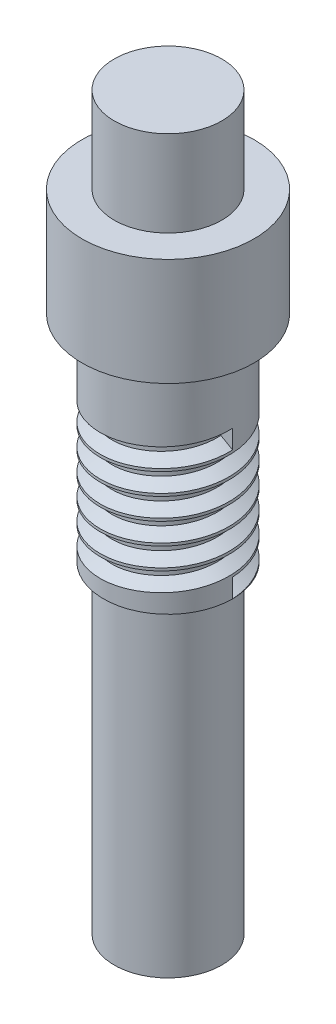
SolidWorks part; units mm, degrees
material "Plain Carbon Steel"
ref_plane "Front Plane" through (0, 0, 0) normal (0, 0, 1) x (1, 0, 0)
ref_plane "Top Plane" through (0, 0, 0) normal (0, 1, 0) x (1, 0, 0)
ref_plane "Right Plane" through (0, 0, 0) normal (1, 0, 0) x (0, 0, -1)
sketch "Sketch1" plane through (0, 0, 0) normal (0, 1, 0) x (1, 0, 0)
  circle A0 centre (0, 0) radius 4
  dimension "D1" = 8
extrude "Boss-Extrude1" add sketch "Sketch1" along normal blind 30
sketch "Sketch8" plane through (0, 0, 0) normal (0, -1, 0) x (1, 0, 0)
  circle A0 centre (0, 0) radius 3
  circle A1 centre (0, 0) radius 4
  dimension "D1" = 6
  dimension "D2" = 8
extrude "Cut-Extrude2" cut sketch "Sketch8" against normal blind 25 contours A0 | A1
ref_plane "Plane1" through (0, 20, 0) normal (0, -1, 0) x (-1, 0, 0)
sketch "Sketch11" plane through (0, 20, 0) normal (0, -1, 0) x (-1, 0, 0)
  circle A0 centre (0, 0) radius 3 construction
  circle A1 centre (0, 0) radius 3
sketch "Sketch14" plane through (0, 0, 0) normal (1, 0, 0) x (0, 0, -1)
  line L0 (3, 20.3816) -> (3, 19.5797)
  line L1 (3, 0) -> (3, 25) construction
  line L2 (3, 0) -> (3, 25) construction
  line L3 (3, 19.5797) -> (2.6675, 20)
  line L4 (-4.4, 20) -> (4.4, 20) construction
  line L5 (2.6675, 20) -> (3, 20.3816)
sketch "Sketch15" plane through (0, 0, 0) normal (0, -1, 0) x (1, 0, 0)
  circle A0 centre (0, 0) radius 3
  circle A1 centre (0, 0) radius 2.5
  dimension "D1" = 5
  dimension "D2" = 6
extrude "Cut-Extrude3" cut sketch "Sketch15" against normal blind 15
thread "Thread1" pitch 1 start angle 0, offset 0, length 0, pitch 1, diameter 6
ref_plane "Plane2" through (3, 15, 0) normal (0, 0, 1) x (1, 0, 0)
sketch "Thread Profile1" plane through (3, 15, 0) normal (0, 0, 1) x (1, 0, 0)
  line L0 (0, 0) -> (0, 1) construction
  line L11 (0, 0) -> (0, 0.875)
  line L12 (0, 0.875) -> (-0.5413, 0.5625)
  line L13 (-0.5413, 0.5625) -> (-0.5413, 0.3125)
  line L15 (-0.5413, 0.3125) -> (0, 0)
  line L17 (-0.5413, 0.4375) -> (0, 0.4375) construction
  point P2 (0, 0)
  dimension "Pitch" = 1
  dimension "Profile_Angle" = 60
  dimension "Profile_Land" = 0.25
  dimension "Profile_Height" = 0.5413
sketch "Sketch18" plane through (0, 30, 0) normal (0, 1, 0) x (1, 0, 0)
  circle A0 centre (0, 0) radius 2.5
  dimension "D1" = 5
extrude "Boss-Extrude2" add sketch "Sketch18" along normal blind 4
